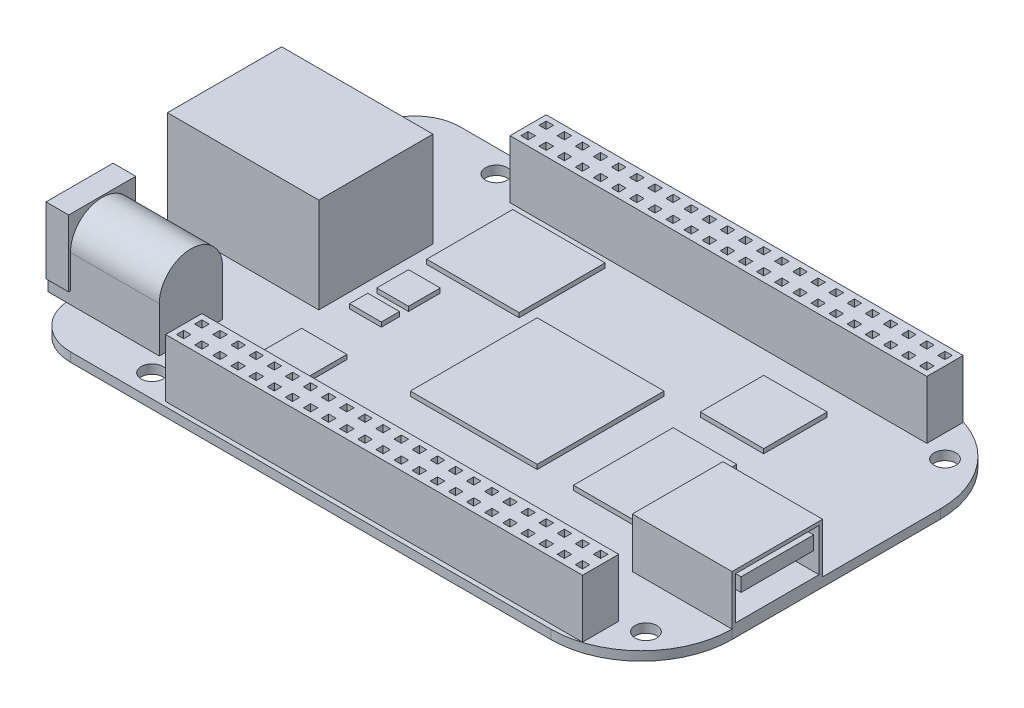
SolidWorks part; units mm, degrees
material "beaglebone"
ref_plane "Front Plane" through (0, 0, 0) normal (0, 0, 1) x (1, 0, 0)
ref_plane "Top Plane" through (0, 0, 0) normal (0, 1, 0) x (1, 0, 0)
ref_plane "Right Plane" through (0, 0, 0) normal (1, 0, 0) x (0, 0, -1)
sketch "Sketch1" plane through (0, 0, 0) normal (0, 1, 0) x (1, 0, 0)
  line L1 (-12.7, 0) -> (-80.01, 0)
  line L2 (0, 12.7) -> (0, 41.91)
  line L3 (-12.7, 54.61) -> (-80.01, 54.61)
  line L4 (-86.36, 6.35) -> (-86.36, 48.26)
  arc A0 (0, 12.7) -> (-12.7, 0) centre (-12.7, 12.7) cw
  arc A1 (0, 41.91) -> (-12.7, 54.61) centre (-12.7, 41.91) ccw
  arc A2 (-86.36, 6.35) -> (-80.01, 0) centre (-80.01, 6.35) ccw
  arc A3 (-86.36, 48.26) -> (-80.01, 54.61) centre (-80.01, 48.26) cw
  point P7 (0, 0)
  point P10 (0, 54.61)
  point P13 (-86.36, 0)
  dimension "D3" = 12.7
  dimension "D4" = 6.35
  dimension "D1" = 86.36
  dimension "D2" = 54.61
extrude "Boss-Extrude1" add sketch "Sketch1" along normal blind 1.27
sketch "Sketch2" plane through (0, 1.27, 0) normal (0, 1, 0) x (1, 0, 0)
  line L0 (-80.01, 0) -> (-12.7, 0) construction
  line L1 (-5.715, 6.35) -> (-71.755, 6.35) construction
  line L2 (-71.755, 51.435) -> (-71.755, 3.175) construction
  line L3 (-86.36, 48.26) -> (-86.36, 6.35) construction
  line L4 (-5.715, 48.26) -> (-5.715, 6.35) construction
  circle A0 centre (-71.755, 51.435) radius 1.524
  circle A1 centre (-71.755, 3.175) radius 1.524
  circle A2 centre (-5.715, 48.26) radius 1.524
  circle A3 centre (-5.715, 6.35) radius 1.524
  dimension "D7" = 3.048
  dimension "D1" = 48.26
  dimension "D2" = 41.91
  dimension "D3" = 6.35
  dimension "D4" = 14.605
  dimension "D5" = 80.645
  dimension "D6" = 3.175
extrude "Cut-Extrude1" cut sketch "Sketch2" along direction (0, -1, 0) on the side against the normal up to surface (1.27 mm away) up to face at (-44.4387, 0, -27.305)
sketch "Sketch3" plane through (0, 1.27, 0) normal (0, 1, 0) x (1, 0, 0)
  line L0 (-10.16, 48.895) -> (-10.16, 50.165) construction
  line L1 (-67.31, 53.975) -> (-8.89, 53.975)
  line L2 (-67.31, 53.975) -> (-67.31, 48.895)
  line L3 (-67.31, 48.895) -> (-8.89, 48.895)
  line L4 (-8.89, 53.975) -> (-8.89, 48.895)
  line L5 (-86.36, 27.305) -> (0, 27.305) construction
  line L6 (0, 12.7) -> (0, 41.91) construction
  line L7 (-66.548, 4.953) -> (-66.548, 3.937)
  line L8 (-66.548, 4.953) -> (-65.532, 4.953)
  line L9 (-10.16, 50.165) -> (-10.16, 52.705) construction
  line L10 (-10.16, 52.705) -> (-10.16, 53.975) construction
  line L11 (-13.208, 52.197) -> (-12.192, 52.197)
  line L12 (-10.668, 53.213) -> (-9.652, 53.213)
  line L13 (-10.668, 53.213) -> (-10.668, 52.197)
  line L14 (-10.668, 52.197) -> (-9.652, 52.197)
  line L15 (-9.652, 53.213) -> (-9.652, 52.197)
  line L16 (-10.668, 53.213) -> (-9.652, 52.197) construction
  line L17 (-10.668, 52.197) -> (-9.652, 53.213) construction
  line L18 (-10.668, 49.657) -> (-9.652, 49.657)
  line L19 (-10.668, 49.657) -> (-10.668, 50.673)
  line L20 (-10.668, 50.673) -> (-9.652, 50.673)
  line L21 (-9.652, 49.657) -> (-9.652, 50.673)
  line L22 (-10.668, 49.657) -> (-9.652, 50.673) construction
  line L23 (-10.668, 50.673) -> (-9.652, 49.657) construction
  line L24 (-13.208, 53.213) -> (-13.208, 52.197)
  line L25 (-13.208, 53.213) -> (-12.192, 53.213)
  line L26 (-12.192, 53.213) -> (-12.192, 52.197)
  line L27 (-13.208, 50.673) -> (-12.192, 50.673)
  line L28 (-12.192, 49.657) -> (-12.192, 50.673)
  line L29 (-13.208, 49.657) -> (-12.192, 49.657)
  line L30 (-13.208, 49.657) -> (-13.208, 50.673)
  line L31 (-15.748, 52.197) -> (-14.732, 52.197)
  line L32 (-15.748, 53.213) -> (-15.748, 52.197)
  line L33 (-15.748, 53.213) -> (-14.732, 53.213)
  line L34 (-14.732, 53.213) -> (-14.732, 52.197)
  line L35 (-15.748, 50.673) -> (-14.732, 50.673)
  line L36 (-14.732, 49.657) -> (-14.732, 50.673)
  line L37 (-15.748, 49.657) -> (-14.732, 49.657)
  line L38 (-15.748, 49.657) -> (-15.748, 50.673)
  line L39 (-18.288, 52.197) -> (-17.272, 52.197)
  line L40 (-18.288, 53.213) -> (-18.288, 52.197)
  line L41 (-18.288, 53.213) -> (-17.272, 53.213)
  line L42 (-17.272, 53.213) -> (-17.272, 52.197)
  line L43 (-18.288, 50.673) -> (-17.272, 50.673)
  line L44 (-17.272, 49.657) -> (-17.272, 50.673)
  line L45 (-18.288, 49.657) -> (-17.272, 49.657)
  line L46 (-18.288, 49.657) -> (-18.288, 50.673)
  line L47 (-20.828, 52.197) -> (-19.812, 52.197)
  line L48 (-20.828, 53.213) -> (-20.828, 52.197)
  line L49 (-20.828, 53.213) -> (-19.812, 53.213)
  line L50 (-19.812, 53.213) -> (-19.812, 52.197)
  line L51 (-20.828, 50.673) -> (-19.812, 50.673)
  line L52 (-19.812, 49.657) -> (-19.812, 50.673)
  line L53 (-20.828, 49.657) -> (-19.812, 49.657)
  line L54 (-20.828, 49.657) -> (-20.828, 50.673)
  line L55 (-23.368, 52.197) -> (-22.352, 52.197)
  line L56 (-23.368, 53.213) -> (-23.368, 52.197)
  line L57 (-23.368, 53.213) -> (-22.352, 53.213)
  line L58 (-22.352, 53.213) -> (-22.352, 52.197)
  line L59 (-23.368, 50.673) -> (-22.352, 50.673)
  line L60 (-22.352, 49.657) -> (-22.352, 50.673)
  line L61 (-23.368, 49.657) -> (-22.352, 49.657)
  line L62 (-23.368, 49.657) -> (-23.368, 50.673)
  line L63 (-25.908, 52.197) -> (-24.892, 52.197)
  line L64 (-25.908, 53.213) -> (-25.908, 52.197)
  line L65 (-25.908, 53.213) -> (-24.892, 53.213)
  line L66 (-24.892, 53.213) -> (-24.892, 52.197)
  line L67 (-25.908, 50.673) -> (-24.892, 50.673)
  line L68 (-24.892, 49.657) -> (-24.892, 50.673)
  line L69 (-25.908, 49.657) -> (-24.892, 49.657)
  line L70 (-25.908, 49.657) -> (-25.908, 50.673)
  line L71 (-28.448, 52.197) -> (-27.432, 52.197)
  line L72 (-28.448, 53.213) -> (-28.448, 52.197)
  line L73 (-28.448, 53.213) -> (-27.432, 53.213)
  line L74 (-27.432, 53.213) -> (-27.432, 52.197)
  line L75 (-28.448, 50.673) -> (-27.432, 50.673)
  line L76 (-27.432, 49.657) -> (-27.432, 50.673)
  line L77 (-28.448, 49.657) -> (-27.432, 49.657)
  line L78 (-28.448, 49.657) -> (-28.448, 50.673)
  line L79 (-30.988, 52.197) -> (-29.972, 52.197)
  line L80 (-30.988, 53.213) -> (-30.988, 52.197)
  line L81 (-30.988, 53.213) -> (-29.972, 53.213)
  line L82 (-29.972, 53.213) -> (-29.972, 52.197)
  line L83 (-30.988, 50.673) -> (-29.972, 50.673)
  line L84 (-29.972, 49.657) -> (-29.972, 50.673)
  line L85 (-30.988, 49.657) -> (-29.972, 49.657)
  line L86 (-30.988, 49.657) -> (-30.988, 50.673)
  line L87 (-33.528, 52.197) -> (-32.512, 52.197)
  line L88 (-33.528, 53.213) -> (-33.528, 52.197)
  line L89 (-33.528, 53.213) -> (-32.512, 53.213)
  line L90 (-32.512, 53.213) -> (-32.512, 52.197)
  line L91 (-33.528, 50.673) -> (-32.512, 50.673)
  line L92 (-32.512, 49.657) -> (-32.512, 50.673)
  line L93 (-33.528, 49.657) -> (-32.512, 49.657)
  line L94 (-33.528, 49.657) -> (-33.528, 50.673)
  line L95 (-36.068, 52.197) -> (-35.052, 52.197)
  line L96 (-36.068, 53.213) -> (-36.068, 52.197)
  line L97 (-36.068, 53.213) -> (-35.052, 53.213)
  line L98 (-35.052, 53.213) -> (-35.052, 52.197)
  line L99 (-36.068, 50.673) -> (-35.052, 50.673)
  line L100 (-35.052, 49.657) -> (-35.052, 50.673)
  line L101 (-36.068, 49.657) -> (-35.052, 49.657)
  line L102 (-36.068, 49.657) -> (-36.068, 50.673)
  line L103 (-38.608, 52.197) -> (-37.592, 52.197)
  line L104 (-38.608, 53.213) -> (-38.608, 52.197)
  line L105 (-38.608, 53.213) -> (-37.592, 53.213)
  line L106 (-37.592, 53.213) -> (-37.592, 52.197)
  line L107 (-38.608, 50.673) -> (-37.592, 50.673)
  line L108 (-37.592, 49.657) -> (-37.592, 50.673)
  line L109 (-38.608, 49.657) -> (-37.592, 49.657)
  line L110 (-38.608, 49.657) -> (-38.608, 50.673)
  line L111 (-41.148, 52.197) -> (-40.132, 52.197)
  line L112 (-41.148, 53.213) -> (-41.148, 52.197)
  line L113 (-41.148, 53.213) -> (-40.132, 53.213)
  line L114 (-40.132, 53.213) -> (-40.132, 52.197)
  line L115 (-41.148, 50.673) -> (-40.132, 50.673)
  line L116 (-40.132, 49.657) -> (-40.132, 50.673)
  line L117 (-41.148, 49.657) -> (-40.132, 49.657)
  line L118 (-41.148, 49.657) -> (-41.148, 50.673)
  line L119 (-43.688, 52.197) -> (-42.672, 52.197)
  line L120 (-43.688, 53.213) -> (-43.688, 52.197)
  line L121 (-43.688, 53.213) -> (-42.672, 53.213)
  line L122 (-42.672, 53.213) -> (-42.672, 52.197)
  line L123 (-43.688, 50.673) -> (-42.672, 50.673)
  line L124 (-42.672, 49.657) -> (-42.672, 50.673)
  line L125 (-43.688, 49.657) -> (-42.672, 49.657)
  line L126 (-43.688, 49.657) -> (-43.688, 50.673)
  line L127 (-46.228, 52.197) -> (-45.212, 52.197)
  line L128 (-46.228, 53.213) -> (-46.228, 52.197)
  line L129 (-46.228, 53.213) -> (-45.212, 53.213)
  line L130 (-45.212, 53.213) -> (-45.212, 52.197)
  line L131 (-46.228, 50.673) -> (-45.212, 50.673)
  line L132 (-45.212, 49.657) -> (-45.212, 50.673)
  line L133 (-46.228, 49.657) -> (-45.212, 49.657)
  line L134 (-46.228, 49.657) -> (-46.228, 50.673)
  line L135 (-48.768, 52.197) -> (-47.752, 52.197)
  line L136 (-48.768, 53.213) -> (-48.768, 52.197)
  line L137 (-48.768, 53.213) -> (-47.752, 53.213)
  line L138 (-47.752, 53.213) -> (-47.752, 52.197)
  line L139 (-48.768, 50.673) -> (-47.752, 50.673)
  line L140 (-47.752, 49.657) -> (-47.752, 50.673)
  line L141 (-48.768, 49.657) -> (-47.752, 49.657)
  line L142 (-48.768, 49.657) -> (-48.768, 50.673)
  line L143 (-51.308, 52.197) -> (-50.292, 52.197)
  line L144 (-51.308, 53.213) -> (-51.308, 52.197)
  line L145 (-51.308, 53.213) -> (-50.292, 53.213)
  line L146 (-50.292, 53.213) -> (-50.292, 52.197)
  line L147 (-51.308, 50.673) -> (-50.292, 50.673)
  line L148 (-50.292, 49.657) -> (-50.292, 50.673)
  line L149 (-51.308, 49.657) -> (-50.292, 49.657)
  line L150 (-51.308, 49.657) -> (-51.308, 50.673)
  line L151 (-53.848, 52.197) -> (-52.832, 52.197)
  line L152 (-53.848, 53.213) -> (-53.848, 52.197)
  line L153 (-53.848, 53.213) -> (-52.832, 53.213)
  line L154 (-52.832, 53.213) -> (-52.832, 52.197)
  line L155 (-53.848, 50.673) -> (-52.832, 50.673)
  line L156 (-52.832, 49.657) -> (-52.832, 50.673)
  line L157 (-53.848, 49.657) -> (-52.832, 49.657)
  line L158 (-53.848, 49.657) -> (-53.848, 50.673)
  line L159 (-56.388, 52.197) -> (-55.372, 52.197)
  line L160 (-56.388, 53.213) -> (-56.388, 52.197)
  line L161 (-56.388, 53.213) -> (-55.372, 53.213)
  line L162 (-55.372, 53.213) -> (-55.372, 52.197)
  line L163 (-56.388, 50.673) -> (-55.372, 50.673)
  line L164 (-55.372, 49.657) -> (-55.372, 50.673)
  line L165 (-56.388, 49.657) -> (-55.372, 49.657)
  line L166 (-56.388, 49.657) -> (-56.388, 50.673)
  line L167 (-58.928, 52.197) -> (-57.912, 52.197)
  line L168 (-58.928, 53.213) -> (-58.928, 52.197)
  line L169 (-58.928, 53.213) -> (-57.912, 53.213)
  line L170 (-57.912, 53.213) -> (-57.912, 52.197)
  line L171 (-58.928, 50.673) -> (-57.912, 50.673)
  line L172 (-57.912, 49.657) -> (-57.912, 50.673)
  line L173 (-58.928, 49.657) -> (-57.912, 49.657)
  line L174 (-58.928, 49.657) -> (-58.928, 50.673)
  line L175 (-61.468, 52.197) -> (-60.452, 52.197)
  line L176 (-61.468, 53.213) -> (-61.468, 52.197)
  line L177 (-61.468, 53.213) -> (-60.452, 53.213)
  line L178 (-60.452, 53.213) -> (-60.452, 52.197)
  line L179 (-61.468, 50.673) -> (-60.452, 50.673)
  line L180 (-60.452, 49.657) -> (-60.452, 50.673)
  line L181 (-61.468, 49.657) -> (-60.452, 49.657)
  line L182 (-61.468, 49.657) -> (-61.468, 50.673)
  line L183 (-64.008, 52.197) -> (-62.992, 52.197)
  line L184 (-64.008, 53.213) -> (-64.008, 52.197)
  line L185 (-64.008, 53.213) -> (-62.992, 53.213)
  line L186 (-62.992, 53.213) -> (-62.992, 52.197)
  line L187 (-64.008, 50.673) -> (-62.992, 50.673)
  line L188 (-62.992, 49.657) -> (-62.992, 50.673)
  line L189 (-64.008, 49.657) -> (-62.992, 49.657)
  line L190 (-64.008, 49.657) -> (-64.008, 50.673)
  line L191 (-66.548, 52.197) -> (-65.532, 52.197)
  line L192 (-66.548, 53.213) -> (-66.548, 52.197)
  line L193 (-66.548, 53.213) -> (-65.532, 53.213)
  line L194 (-65.532, 53.213) -> (-65.532, 52.197)
  line L195 (-66.548, 50.673) -> (-65.532, 50.673)
  line L196 (-65.532, 49.657) -> (-65.532, 50.673)
  line L197 (-66.548, 49.657) -> (-65.532, 49.657)
  line L198 (-66.548, 49.657) -> (-66.548, 50.673)
  line L199 (-66.548, 49.657) -> (-65.532, 50.673) construction
  line L200 (-86.36, 48.26) -> (-86.36, 6.35) construction
  line L201 (-65.532, 4.953) -> (-65.532, 3.937)
  line L202 (-12.7, 54.61) -> (-80.01, 54.61) construction
  line L203 (-66.548, 3.937) -> (-65.532, 3.937)
  line L204 (-65.532, 1.397) -> (-65.532, 2.413)
  line L205 (-66.548, 1.397) -> (-65.532, 1.397)
  line L206 (-66.548, 1.397) -> (-66.548, 2.413)
  line L207 (-66.548, 2.413) -> (-65.532, 2.413)
  line L208 (-64.008, 4.953) -> (-64.008, 3.937)
  line L209 (-64.008, 4.953) -> (-62.992, 4.953)
  line L210 (-62.992, 4.953) -> (-62.992, 3.937)
  line L211 (-64.008, 3.937) -> (-62.992, 3.937)
  line L212 (-62.992, 1.397) -> (-62.992, 2.413)
  line L213 (-64.008, 1.397) -> (-62.992, 1.397)
  line L214 (-64.008, 1.397) -> (-64.008, 2.413)
  line L215 (-64.008, 2.413) -> (-62.992, 2.413)
  line L216 (-61.468, 4.953) -> (-61.468, 3.937)
  line L217 (-61.468, 4.953) -> (-60.452, 4.953)
  line L218 (-60.452, 4.953) -> (-60.452, 3.937)
  line L219 (-61.468, 3.937) -> (-60.452, 3.937)
  line L220 (-60.452, 1.397) -> (-60.452, 2.413)
  line L221 (-61.468, 1.397) -> (-60.452, 1.397)
  line L222 (-61.468, 1.397) -> (-61.468, 2.413)
  line L223 (-61.468, 2.413) -> (-60.452, 2.413)
  line L224 (-58.928, 4.953) -> (-58.928, 3.937)
  line L225 (-58.928, 4.953) -> (-57.912, 4.953)
  line L226 (-57.912, 4.953) -> (-57.912, 3.937)
  line L227 (-58.928, 3.937) -> (-57.912, 3.937)
  line L228 (-57.912, 1.397) -> (-57.912, 2.413)
  line L229 (-58.928, 1.397) -> (-57.912, 1.397)
  line L230 (-58.928, 1.397) -> (-58.928, 2.413)
  line L231 (-58.928, 2.413) -> (-57.912, 2.413)
  line L232 (-56.388, 4.953) -> (-56.388, 3.937)
  line L233 (-56.388, 4.953) -> (-55.372, 4.953)
  line L234 (-55.372, 4.953) -> (-55.372, 3.937)
  line L235 (-56.388, 3.937) -> (-55.372, 3.937)
  line L236 (-55.372, 1.397) -> (-55.372, 2.413)
  line L237 (-56.388, 1.397) -> (-55.372, 1.397)
  line L238 (-56.388, 1.397) -> (-56.388, 2.413)
  line L239 (-56.388, 2.413) -> (-55.372, 2.413)
  line L240 (-53.848, 4.953) -> (-53.848, 3.937)
  line L241 (-53.848, 4.953) -> (-52.832, 4.953)
  line L242 (-52.832, 4.953) -> (-52.832, 3.937)
  line L243 (-53.848, 3.937) -> (-52.832, 3.937)
  line L244 (-52.832, 1.397) -> (-52.832, 2.413)
  line L245 (-53.848, 1.397) -> (-52.832, 1.397)
  line L246 (-53.848, 1.397) -> (-53.848, 2.413)
  line L247 (-53.848, 2.413) -> (-52.832, 2.413)
  line L248 (-51.308, 4.953) -> (-51.308, 3.937)
  line L249 (-51.308, 4.953) -> (-50.292, 4.953)
  line L250 (-50.292, 4.953) -> (-50.292, 3.937)
  line L251 (-51.308, 3.937) -> (-50.292, 3.937)
  line L252 (-50.292, 1.397) -> (-50.292, 2.413)
  line L253 (-51.308, 1.397) -> (-50.292, 1.397)
  line L254 (-51.308, 1.397) -> (-51.308, 2.413)
  line L255 (-51.308, 2.413) -> (-50.292, 2.413)
  line L256 (-48.768, 4.953) -> (-48.768, 3.937)
  line L257 (-48.768, 4.953) -> (-47.752, 4.953)
  line L258 (-47.752, 4.953) -> (-47.752, 3.937)
  line L259 (-48.768, 3.937) -> (-47.752, 3.937)
  line L260 (-47.752, 1.397) -> (-47.752, 2.413)
  line L261 (-48.768, 1.397) -> (-47.752, 1.397)
  line L262 (-48.768, 1.397) -> (-48.768, 2.413)
  line L263 (-48.768, 2.413) -> (-47.752, 2.413)
  line L264 (-46.228, 4.953) -> (-46.228, 3.937)
  line L265 (-46.228, 4.953) -> (-45.212, 4.953)
  line L266 (-45.212, 4.953) -> (-45.212, 3.937)
  line L267 (-46.228, 3.937) -> (-45.212, 3.937)
  line L268 (-45.212, 1.397) -> (-45.212, 2.413)
  line L269 (-46.228, 1.397) -> (-45.212, 1.397)
  line L270 (-46.228, 1.397) -> (-46.228, 2.413)
  line L271 (-46.228, 2.413) -> (-45.212, 2.413)
  line L272 (-43.688, 4.953) -> (-43.688, 3.937)
  line L273 (-43.688, 4.953) -> (-42.672, 4.953)
  line L274 (-42.672, 4.953) -> (-42.672, 3.937)
  line L275 (-43.688, 3.937) -> (-42.672, 3.937)
  line L276 (-42.672, 1.397) -> (-42.672, 2.413)
  line L277 (-43.688, 1.397) -> (-42.672, 1.397)
  line L278 (-43.688, 1.397) -> (-43.688, 2.413)
  line L279 (-43.688, 2.413) -> (-42.672, 2.413)
  line L280 (-41.148, 4.953) -> (-41.148, 3.937)
  line L281 (-41.148, 4.953) -> (-40.132, 4.953)
  line L282 (-40.132, 4.953) -> (-40.132, 3.937)
  line L283 (-41.148, 3.937) -> (-40.132, 3.937)
  line L284 (-40.132, 1.397) -> (-40.132, 2.413)
  line L285 (-41.148, 1.397) -> (-40.132, 1.397)
  line L286 (-41.148, 1.397) -> (-41.148, 2.413)
  line L287 (-41.148, 2.413) -> (-40.132, 2.413)
  line L288 (-38.608, 4.953) -> (-38.608, 3.937)
  line L289 (-38.608, 4.953) -> (-37.592, 4.953)
  line L290 (-37.592, 4.953) -> (-37.592, 3.937)
  line L291 (-38.608, 3.937) -> (-37.592, 3.937)
  line L292 (-37.592, 1.397) -> (-37.592, 2.413)
  line L293 (-38.608, 1.397) -> (-37.592, 1.397)
  line L294 (-38.608, 1.397) -> (-38.608, 2.413)
  line L295 (-38.608, 2.413) -> (-37.592, 2.413)
  line L296 (-36.068, 4.953) -> (-36.068, 3.937)
  line L297 (-36.068, 4.953) -> (-35.052, 4.953)
  line L298 (-35.052, 4.953) -> (-35.052, 3.937)
  line L299 (-36.068, 3.937) -> (-35.052, 3.937)
  line L300 (-35.052, 1.397) -> (-35.052, 2.413)
  line L301 (-36.068, 1.397) -> (-35.052, 1.397)
  line L302 (-36.068, 1.397) -> (-36.068, 2.413)
  line L303 (-36.068, 2.413) -> (-35.052, 2.413)
  line L304 (-33.528, 4.953) -> (-33.528, 3.937)
  line L305 (-33.528, 4.953) -> (-32.512, 4.953)
  line L306 (-32.512, 4.953) -> (-32.512, 3.937)
  line L307 (-33.528, 3.937) -> (-32.512, 3.937)
  line L308 (-32.512, 1.397) -> (-32.512, 2.413)
  line L309 (-33.528, 1.397) -> (-32.512, 1.397)
  line L310 (-33.528, 1.397) -> (-33.528, 2.413)
  line L311 (-33.528, 2.413) -> (-32.512, 2.413)
  line L312 (-30.988, 4.953) -> (-30.988, 3.937)
  line L313 (-30.988, 4.953) -> (-29.972, 4.953)
  line L314 (-29.972, 4.953) -> (-29.972, 3.937)
  line L315 (-30.988, 3.937) -> (-29.972, 3.937)
  line L316 (-29.972, 1.397) -> (-29.972, 2.413)
  line L317 (-30.988, 1.397) -> (-29.972, 1.397)
  line L318 (-30.988, 1.397) -> (-30.988, 2.413)
  line L319 (-30.988, 2.413) -> (-29.972, 2.413)
  line L320 (-28.448, 4.953) -> (-28.448, 3.937)
  line L321 (-28.448, 4.953) -> (-27.432, 4.953)
  line L322 (-27.432, 4.953) -> (-27.432, 3.937)
  line L323 (-28.448, 3.937) -> (-27.432, 3.937)
  line L324 (-27.432, 1.397) -> (-27.432, 2.413)
  line L325 (-28.448, 1.397) -> (-27.432, 1.397)
  line L326 (-28.448, 1.397) -> (-28.448, 2.413)
  line L327 (-28.448, 2.413) -> (-27.432, 2.413)
  line L328 (-25.908, 4.953) -> (-25.908, 3.937)
  line L329 (-25.908, 4.953) -> (-24.892, 4.953)
  line L330 (-24.892, 4.953) -> (-24.892, 3.937)
  line L331 (-25.908, 3.937) -> (-24.892, 3.937)
  line L332 (-24.892, 1.397) -> (-24.892, 2.413)
  line L333 (-25.908, 1.397) -> (-24.892, 1.397)
  line L334 (-25.908, 1.397) -> (-25.908, 2.413)
  line L335 (-25.908, 2.413) -> (-24.892, 2.413)
  line L336 (-23.368, 4.953) -> (-23.368, 3.937)
  line L337 (-23.368, 4.953) -> (-22.352, 4.953)
  line L338 (-22.352, 4.953) -> (-22.352, 3.937)
  line L339 (-23.368, 3.937) -> (-22.352, 3.937)
  line L340 (-22.352, 1.397) -> (-22.352, 2.413)
  line L341 (-23.368, 1.397) -> (-22.352, 1.397)
  line L342 (-23.368, 1.397) -> (-23.368, 2.413)
  line L343 (-23.368, 2.413) -> (-22.352, 2.413)
  line L344 (-20.828, 4.953) -> (-20.828, 3.937)
  line L345 (-20.828, 4.953) -> (-19.812, 4.953)
  line L346 (-19.812, 4.953) -> (-19.812, 3.937)
  line L347 (-20.828, 3.937) -> (-19.812, 3.937)
  line L348 (-19.812, 1.397) -> (-19.812, 2.413)
  line L349 (-20.828, 1.397) -> (-19.812, 1.397)
  line L350 (-20.828, 1.397) -> (-20.828, 2.413)
  line L351 (-20.828, 2.413) -> (-19.812, 2.413)
  line L352 (-18.288, 4.953) -> (-18.288, 3.937)
  line L353 (-18.288, 4.953) -> (-17.272, 4.953)
  line L354 (-17.272, 4.953) -> (-17.272, 3.937)
  line L355 (-18.288, 3.937) -> (-17.272, 3.937)
  line L356 (-17.272, 1.397) -> (-17.272, 2.413)
  line L357 (-18.288, 1.397) -> (-17.272, 1.397)
  line L358 (-18.288, 1.397) -> (-18.288, 2.413)
  line L359 (-18.288, 2.413) -> (-17.272, 2.413)
  line L360 (-15.748, 4.953) -> (-15.748, 3.937)
  line L361 (-15.748, 4.953) -> (-14.732, 4.953)
  line L362 (-14.732, 4.953) -> (-14.732, 3.937)
  line L363 (-15.748, 3.937) -> (-14.732, 3.937)
  line L364 (-14.732, 1.397) -> (-14.732, 2.413)
  line L365 (-15.748, 1.397) -> (-14.732, 1.397)
  line L366 (-15.748, 1.397) -> (-15.748, 2.413)
  line L367 (-15.748, 2.413) -> (-14.732, 2.413)
  line L368 (-13.208, 4.953) -> (-13.208, 3.937)
  line L369 (-13.208, 4.953) -> (-12.192, 4.953)
  line L370 (-12.192, 4.953) -> (-12.192, 3.937)
  line L371 (-13.208, 3.937) -> (-12.192, 3.937)
  line L372 (-12.192, 1.397) -> (-12.192, 2.413)
  line L373 (-13.208, 1.397) -> (-12.192, 1.397)
  line L374 (-13.208, 1.397) -> (-13.208, 2.413)
  line L375 (-9.652, 4.953) -> (-9.652, 3.937)
  line L376 (-10.668, 3.937) -> (-9.652, 3.937)
  line L377 (-10.668, 4.953) -> (-10.668, 3.937)
  line L378 (-10.668, 4.953) -> (-9.652, 4.953)
  line L379 (-9.652, 1.397) -> (-9.652, 2.413)
  line L380 (-10.668, 2.413) -> (-9.652, 2.413)
  line L381 (-10.668, 1.397) -> (-10.668, 2.413)
  line L382 (-10.668, 1.397) -> (-9.652, 1.397)
  line L383 (-13.208, 2.413) -> (-12.192, 2.413)
  line L384 (-8.89, 0.635) -> (-8.89, 5.715)
  line L385 (-67.31, 5.715) -> (-8.89, 5.715)
  line L386 (-67.31, 0.635) -> (-67.31, 5.715)
  line L387 (-67.31, 0.635) -> (-8.89, 0.635)
  circle A0 centre (-66.04, 50.165) radius 0.1361
  dimension "D1" = 1.016
  dimension "D2" = 2.54
  dimension "D3" = 5.08
  dimension "D4" = 58.42
  dimension "D5" = 1.27
  dimension "D7" = 20.32
  dimension "D8" = 0.635
  dimension "D6" = 23
extrude "Boss-Extrude2" add sketch "Sketch3" along normal blind 8.128 contours L4 L1 L2 L3 L193 L194 L191 L192 L185 L186 L183 L184 L177 L178 L175 L176 L169 L170 L167 L168 L161 L162 L159 L160 L153 L154 L151 L152 L145 L146 L143 L144 L137 L138 L135 L136 L129 L130 L127 L128 L121 | L386 L387 L384 L385 L374 L383 L372 L373 L382 L381 L380 L379 L366 L367 L364 L365 L363 L360 L361 L362 L350 L351 L348 L349 L347 L344 L345 L346 L334 L335 L332 L333 L331 L328 L329 L330 L318 L319 L316 L317 L315 region at (-38.1, 1.27, -51.435) region at (-38.1, 1.27, -3.175)
sketch "Sketch4" plane through (0, 1.27, 0) normal (0, 1, 0) x (1, 0, 0)
  line L0 (-86.36, 48.26) -> (-86.36, 6.35) construction
  line L1 (-67.691, 22.479) -> (-88.9, 22.479)
  line L2 (-67.691, 22.479) -> (-67.691, 38.481)
  line L3 (-67.691, 38.481) -> (-88.9, 38.481)
  line L4 (-88.9, 22.479) -> (-88.9, 38.481)
  line L5 (-12.7, 54.61) -> (-80.01, 54.61) construction
  dimension "D1" = 2.54
  dimension "D2" = 21.209
  dimension "D3" = 16.002
  dimension "D4" = 16.129
extrude "Boss-Extrude3" add sketch "Sketch4" along normal blind 13.335
sketch "Sketch5" plane through (-88.9, 0, 0) normal (-1, 0, 0) x (0, 0, 1)
  line L0 (-30.48, 2.286) -> (-30.48, 3.937) construction
  line L1 (-36.83, 12.065) -> (-24.13, 12.065)
  line L2 (-36.83, 12.065) -> (-36.83, 5.461)
  line L3 (-36.83, 5.461) -> (-24.13, 5.461)
  line L4 (-24.13, 12.065) -> (-24.13, 5.461)
  line L5 (-33.655, 5.461) -> (-27.305, 5.461)
  line L6 (-33.655, 5.461) -> (-33.655, 3.937)
  line L7 (-33.655, 3.937) -> (-27.305, 3.937)
  line L8 (-27.305, 5.461) -> (-27.305, 3.937)
  line L9 (-32.512, 3.937) -> (-28.448, 3.937)
  line L10 (-32.512, 3.937) -> (-32.512, 2.286)
  line L11 (-32.512, 2.286) -> (-28.448, 2.286)
  line L12 (-28.448, 3.937) -> (-28.448, 2.286)
  line L13 (-30.48, 3.937) -> (-30.48, 5.461) construction
  line L14 (-38.481, 14.605) -> (-22.479, 14.605) construction
  line L15 (-36.83, 12.065) -> (-38.481, 12.065) construction
  line L16 (-38.481, 14.605) -> (-38.481, 1.27) construction
  line L17 (-24.13, 12.065) -> (-22.479, 12.065) construction
  line L18 (-22.479, 14.605) -> (-22.479, 1.27) construction
  dimension "D1" = 12.7
  dimension "D2" = 6.604
  dimension "D3" = 2.54
  dimension "D4" = 1.524
  dimension "D5" = 1.651
  dimension "D6" = 4.064
  dimension "D7" = 6.35
extrude "Cut-Extrude2" cut sketch "Sketch5" against normal blind 17.78 contours L4 L1 L2 L3 | L8 L3 L6 L7 | L12 L7 L10 L11 region at (-88.9, 8.763, -30.48) region at (-88.9, 4.699, -30.48) region at (-88.9, 3.1115, -30.48)
sketch "Sketch6" plane through (0, 1.27, 0) normal (0, 1, 0) x (1, 0, 0)
  line L0 (-67.31, 48.895) -> (-8.89, 48.895) construction
  line L1 (-65.659, 35.56) -> (-52.705, 35.56)
  line L2 (-65.659, 35.56) -> (-65.659, 47.625)
  line L3 (-65.659, 47.625) -> (-52.705, 47.625)
  line L4 (-52.705, 35.56) -> (-52.705, 47.625)
  line L5 (-50.8, 36.195) -> (-33.02, 36.195)
  line L6 (-50.8, 36.195) -> (-50.8, 18.415)
  line L7 (-50.8, 18.415) -> (-33.02, 18.415)
  line L8 (-33.02, 36.195) -> (-33.02, 18.415)
  line L9 (-27.94, 45.085) -> (-19.05, 45.085)
  line L10 (-27.94, 45.085) -> (-27.94, 36.195)
  line L11 (-27.94, 36.195) -> (-19.05, 36.195)
  line L12 (-19.05, 45.085) -> (-19.05, 36.195)
  line L13 (-27.94, 32.385) -> (-19.05, 32.385)
  line L14 (-27.94, 32.385) -> (-27.94, 18.415)
  line L15 (-27.94, 18.415) -> (-19.05, 18.415)
  line L16 (-19.05, 32.385) -> (-19.05, 18.415)
  line L17 (-66.04, 18.415) -> (-59.69, 18.415)
  line L18 (-66.04, 18.415) -> (-66.04, 12.065)
  line L19 (-66.04, 12.065) -> (-59.69, 12.065)
  line L20 (-59.69, 18.415) -> (-59.69, 12.065)
  line L21 (-65.659, 27.305) -> (-61.214, 27.305)
  line L22 (-65.659, 27.305) -> (-65.659, 24.765)
  line L23 (-65.659, 24.765) -> (-61.214, 24.765)
  line L24 (-61.214, 27.305) -> (-61.214, 24.765)
  line L25 (-65.659, 33.02) -> (-61.214, 33.02)
  line L26 (-65.659, 33.02) -> (-65.659, 28.575)
  line L27 (-65.659, 28.575) -> (-61.214, 28.575)
  line L28 (-61.214, 33.02) -> (-61.214, 28.575)
  line L29 (0, 12.7) -> (0, 41.91) construction
  line L30 (-67.31, 48.895) -> (-8.89, 48.895) construction
  line L31 (-67.31, 5.715) -> (-8.89, 5.715) construction
  line L33 (-67.31, 0.635) -> (-67.31, 5.715) construction
  dimension "D1" = 8.89
  dimension "D2" = 13.97
  dimension "D3" = 3.81
  dimension "D4" = 3.81
  dimension "D5" = 19.05
  dimension "D6" = 17.78
  dimension "D7" = 12.7
  dimension "D8" = 33.02
  dimension "D9" = 12.954
  dimension "D10" = 12.065
  dimension "D11" = 1.905
  dimension "D12" = 4.445
  dimension "D13" = 2.54
  dimension "D14" = 1.27
  dimension "D15" = 2.54
  dimension "D16" = 1.27
  dimension "D17" = 6.35
  dimension "D18" = 6.35
  dimension "D19" = 1.27
extrude "Boss-Extrude4" add sketch "Sketch6" along normal blind 0.635
sketch "Sketch7" plane through (0, 1.27, 0) normal (0, 1, 0) x (1, 0, 0)
  line L1 (0, 12.7) -> (-13.97, 12.7)
  line L2 (0, 12.7) -> (0, 25.4)
  line L3 (0, 25.4) -> (-13.97, 25.4)
  line L4 (-13.97, 12.7) -> (-13.97, 25.4)
  line L5 (-80.01, 0) -> (-12.7, 0) construction
  line L6 (0, 12.7) -> (0, 41.91) construction
  dimension "D1" = 12.7
  dimension "D2" = 13.97
  dimension "D3" = 25.4
extrude "Boss-Extrude5" add sketch "Sketch7" along normal blind 6.985
sketch "Sketch8" plane through (0, 0, 0) normal (1, 0, 0) x (0, 0, -1)
  line L0 (12.7, 8.255) -> (25.4, 8.255) construction
  line L1 (13.97, 6.985) -> (24.13, 6.985)
  line L2 (13.97, 6.985) -> (13.97, 5.08)
  line L3 (13.97, 5.08) -> (24.13, 5.08)
  line L4 (24.13, 6.985) -> (24.13, 5.08)
  line L5 (13.208, 7.747) -> (24.892, 7.747)
  line L6 (13.208, 7.747) -> (13.208, 1.778)
  line L7 (13.208, 1.778) -> (24.892, 1.778)
  line L8 (24.892, 7.747) -> (24.892, 1.778)
  line L9 (25.4, 8.255) -> (25.4, 1.27) construction
  line L10 (12.7, 8.255) -> (12.7, 1.27) construction
  line L11 (12.7, 1.27) -> (0, 1.27) construction
  line L12 (13.97, 7.18) -> (13.208, 7.18) construction
  line L14 (24.892, 6.9479) -> (24.13, 6.9479) construction
  dimension "D1" = 0.508
  dimension "D2" = 0.508
  dimension "D3" = 0.508
  dimension "D4" = 0.508
  dimension "D5" = 1.905
  dimension "D6" = 10.16
  dimension "D7" = 3.175
extrude "Cut-Extrude3" cut sketch "Sketch8" against normal blind 12.7
sketch "Sketch9" plane through (0, 1.27, 0) normal (0, 1, 0) x (1, 0, 0)
  line L0 (-88.9, 38.481) -> (-88.9, 22.479) construction
  line L1 (-73.279, 5.715) -> (-88.9, 5.715)
  line L2 (-73.279, 5.715) -> (-73.279, 14.605)
  line L3 (-73.279, 14.605) -> (-88.9, 14.605)
  line L4 (-88.9, 5.715) -> (-88.9, 14.605)
  line L5 (-67.31, 5.715) -> (-8.89, 5.715) construction
  circle A0 centre (-71.755, 3.175) radius 1.524 construction
  dimension "D1" = 8.89
extrude "Boss-Extrude6" add sketch "Sketch9" along normal blind 6.35
sketch "Sketch10" plane through (-88.9, 0, 0) normal (-1, 0, 0) x (0, 0, 1)
  line L0 (-14.605, 7.62) -> (-5.715, 7.62) construction
  circle A0 centre (-10.16, 7.62) radius 4.445
  circle A1 centre (-10.16, 7.62) radius 3.4925
  circle A2 centre (-10.16, 7.62) radius 0.635
  line M3 (-5.715, 7.62) -> (-14.605, 7.62)
  dimension "D1" = 1.27
  dimension "D2" = 6.985
extrude "Boss-Extrude7" add sketch "Sketch10" along direction (1, 0, 0) on the side against the normal up to surface (15.621 mm away) contours A1 A0 M3 | A1 A0 M3 | A2 M3 | A2 A1 M3 region at (-88.9, 7.7194, -6.1912) region at (-88.9, 3.2744, -10.16) region at (-88.9, 9.1437, -10.16) region at (-88.9, 7.8895, -10.16) up to face at (-73.279, 4.445, -10.16)
sketch "Sketch11" plane through (-88.9, 0, 0) normal (-1, 0, 0) x (0, 0, 1)
  line L0 (-14.605, 7.62) -> (-14.605, 1.27) construction
  line L1 (-5.461, 2.952) -> (-14.859, 2.952)
  line L2 (-5.461, 2.952) -> (-5.461, 12.288)
  line L3 (-5.461, 12.288) -> (-14.859, 12.288)
  line L4 (-14.859, 2.952) -> (-14.859, 12.288)
  line L5 (-5.461, 2.952) -> (-14.859, 12.288) construction
  line L6 (-5.461, 12.288) -> (-14.859, 2.952) construction
  point P0 (-10.16, 7.62)
  dimension "D1" = 0.254
extrude "Boss-Extrude8" add sketch "Sketch11" against normal blind 3.175
extrude "Cut-Extrude4" cut sketch "Sketch10<3>" against normal blind 12.7 contours A2 A1 M3 | A2 A1 M3 region at (-88.9, 9.1437, -10.16) region at (-88.9, 6.0963, -10.16)
sketch "Sketch10<3>" plane through (-88.9, 0, 0) normal (-1, 0, 0) x (0, 0, 1) same geometry as "Sketch10"
fillet "Fillet1" radius 0.635 1 edges at (-88.9, 7.62, -9.525)
ref_plane "MidPlane" through (-43.18, 0, 0) normal (-1, 0, 0) x (0, 0, 1)
ref_plane "Vertical Plane" through (0, 0, -27.305) normal (0, 0, 1) x (1, 0, 0)
sketch "Sketch12" plane through (0, 0, 0) normal (0, 1, 0) x (1, 0, 0)
  line L0 (-71.755, 51.435) -> (-71.755, 3.175) construction
  line L1 (-86.36, 40.6203) -> (0, 40.6203)
  line L2 (-86.36, 48.26) -> (-86.36, 38.481) construction
  line L3 (0, 25.4) -> (0, 41.91) construction
  line L4 (-5.715, 48.26) -> (-5.715, 6.35) construction
  point P10 (-43.18, 40.6203)
